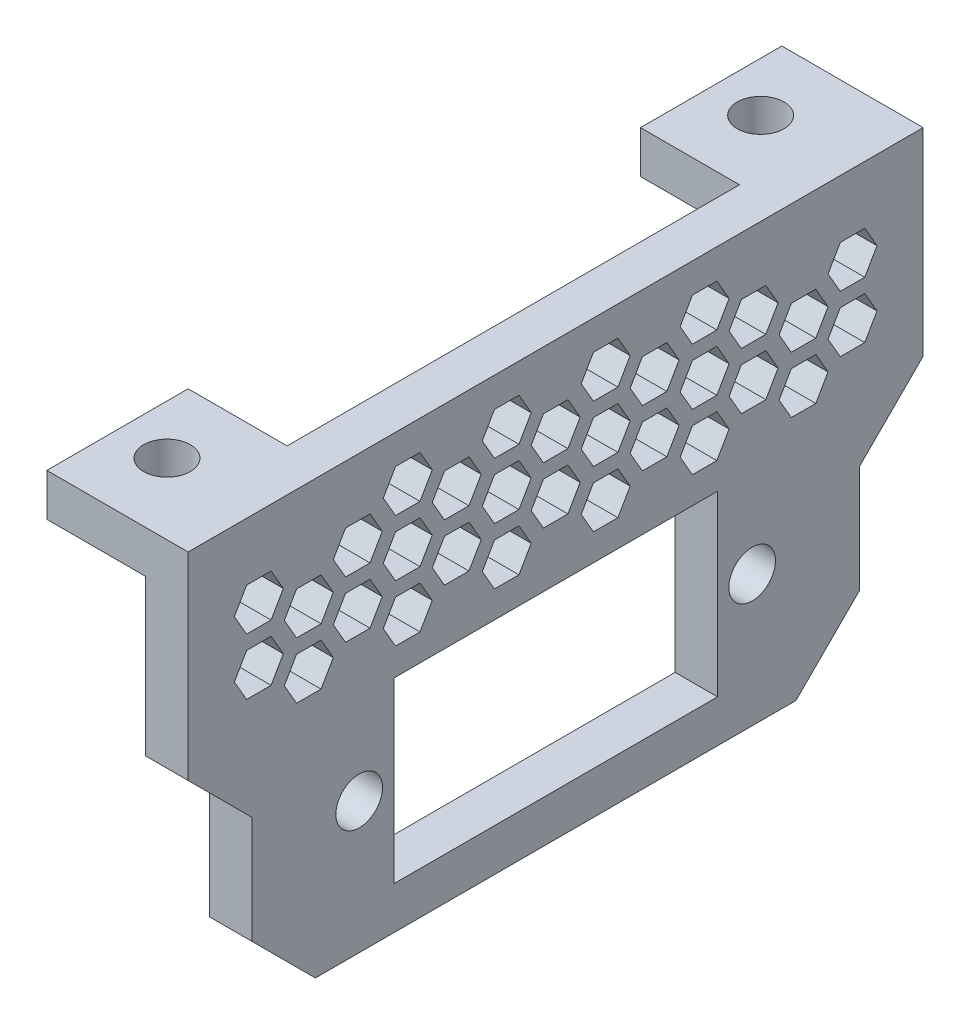
SolidWorks part; units mm, degrees
ref_plane "Front Plane" through (0, 0, 0) normal (0, 0, 1) x (1, 0, 0)
ref_plane "Top Plane" through (0, 0, 0) normal (0, 1, 0) x (1, 0, 0)
ref_plane "Right Plane" through (0, 0, 0) normal (1, 0, 0) x (0, 0, -1)
sketch "Sketch1" plane through (0, 0, 0) normal (1, 0, 0) x (0, 0, -1)
  line L0 (-11.45, 0) -> (11.45, 0)
  line L1 (11.45, 0) -> (11.45, 12.6)
  line L2 (11.45, 12.6) -> (-11.45, 12.6)
  line L3 (-11.45, 12.6) -> (-11.45, 0)
  line L4 (17, -3) -> (-17, -3)
  line L5 (-17, -3) -> (-17, 15.6)
  line L6 (-17, 15.6) -> (17, 15.6)
  line L7 (17, 15.6) -> (17, -3)
  line L8 (0, 0) -> (0, 6.3) construction
  line L9 (-13.9, 6.3) -> (13.9, 6.3)
  circle A0 centre (-13.9, 6.3) radius 1.65
  circle A1 centre (13.9, 6.3) radius 1.65
  point P4 (0, 0)
  point P9 (0, -3)
  point P20 (0, 6.3)
  dimension "D7" = 3.3
  dimension "D8" = 27.8
  dimension "D1" = 22.9
  dimension "D2" = 12.6
  dimension "D3" = 3
  dimension "D4" = 3
  dimension "D5" = 34
  dimension "D6" = 6.3
extrude "Boss-Extrude1" add sketch "Sketch1" along normal blind 3 contours L7 L6 L5 L4 A1 L1 L0 L3 A0 L2 region at (0, -2.6124, 0)
sketch "Sketch2" plane through (0, 0, 0) normal (-1, 0, 0) x (0, 0, 1)
  line L6 (-21.5, 1.5) -> (-17, -3)
  line L8 (17, -3) -> (21.5, 1.5)
  line L9 (21.5, 1.5) -> (21.5, 9.1)
  line L12 (-21.5, 1.5) -> (-21.5, 9.1)
  line L13 (-21.5, 9.1) -> (-26, 13.6)
  line L14 (-26, 13.6) -> (-26, 27.6)
  line L15 (-26, 27.6) -> (26, 27.6)
  line L16 (26, 27.6) -> (26, 13.6)
  line L17 (26, 13.6) -> (21.5, 9.1)
  line L20 (17, -3) -> (17, 15.6)
  line L21 (17, 15.6) -> (-17, 15.6)
  line L22 (-17, 15.6) -> (-17, -3)
  line M10 (-17, 15.6) -> (-17, -3)
  line M12 (17, -3) -> (17, 15.6)
  dimension "D1" = 52
  dimension "D2" = 12
  dimension "D3" = 45
  dimension "D4" = 4.5
  dimension "D5" = 4.5
  dimension "D6" = 135
  dimension "D7" = 14
  dimension "D8" = 14
  dimension "D9" = 9
extrude "Boss-Extrude2" add sketch "Sketch2" against normal blind 3 contours M12 | L13 M10 region at (0, 18.6202, 0)
sketch "Sketch3" plane through (0, 27.6, 0) normal (0, 1, 0) x (1, 0, 0)
  line L1 (0, -26) -> (-7, -26)
  line L2 (0, -26) -> (0, -16)
  line L3 (0, -16) -> (-7, -16)
  line L4 (-7, -26) -> (-7, -16)
  line L5 (3, -26) -> (0, -26) construction
  line L6 (0, 16) -> (-7, 16)
  line L7 (0, 16) -> (0, 26)
  line L8 (0, 26) -> (-7, 26)
  line L9 (-7, 16) -> (-7, 26)
  line L10 (3, 26) -> (0, 26) construction
  circle A0 centre (-3.5, -21) radius 1.65
  circle A1 centre (-3.5, 21) radius 1.65
  dimension "D6" = 3.3
  dimension "D8" = 3.5
  dimension "D9" = 3.5
  dimension "D10" = 5
  dimension "D2" = 42
  dimension "D3" = 10
  dimension "D4" = 10
  dimension "D5" = 7
extrude "Boss-Extrude3" add sketch "Sketch3" against normal blind 3
sketch "Sketch4" plane through (0, 0, 0) normal (-1, 0, 0) x (0, 0, 1)
  line L0 (-15.8038, 20) -> (-16.6699, 21.5)
  line L1 (-19.2679, 18) -> (-20.134, 19.5)
  line L2 (-20.134, 19.5) -> (-21.866, 19.5)
  line L3 (-21.866, 19.5) -> (-22.7321, 18)
  line L4 (-22.7321, 18) -> (-21.866, 16.5)
  line L5 (-21.866, 16.5) -> (-20.134, 16.5)
  line L6 (-20.134, 16.5) -> (-19.2679, 18)
  line L7 (-16.6699, 21.5) -> (-18.4019, 21.5)
  line L8 (-18.4019, 21.5) -> (-19.2679, 20)
  line L9 (-19.2679, 20) -> (-18.4019, 18.5)
  line L10 (-18.4019, 18.5) -> (-16.6699, 18.5)
  line L11 (-16.6699, 18.5) -> (-15.8038, 20)
  line L18 (-19.2679, 22) -> (-20.134, 23.5)
  line L19 (-20.134, 23.5) -> (-21.866, 23.5)
  line L20 (-21.866, 23.5) -> (-22.7321, 22)
  line L21 (-22.7321, 22) -> (-21.866, 20.5)
  line L22 (-21.866, 20.5) -> (-20.134, 20.5)
  line L23 (-20.134, 20.5) -> (-19.2679, 22)
  line L24 (-12.2679, 18) -> (-13.134, 19.5)
  line L25 (-13.134, 19.5) -> (-14.866, 19.5)
  line L26 (-14.866, 19.5) -> (-15.7321, 18)
  line L27 (-15.7321, 18) -> (-14.866, 16.5)
  line L28 (-14.866, 16.5) -> (-13.134, 16.5)
  line L29 (-13.134, 16.5) -> (-12.2679, 18)
  line L30 (-12.2679, 22) -> (-13.134, 23.5)
  line L31 (-13.134, 23.5) -> (-14.866, 23.5)
  line L32 (-14.866, 23.5) -> (-15.7321, 22)
  line L33 (-15.7321, 22) -> (-14.866, 20.5)
  line L34 (-14.866, 20.5) -> (-13.134, 20.5)
  line L35 (-13.134, 20.5) -> (-12.2679, 22)
  line L36 (-5.2679, 18) -> (-6.134, 19.5)
  line L37 (-6.134, 19.5) -> (-7.866, 19.5)
  line L38 (-7.866, 19.5) -> (-8.7321, 18)
  line L39 (-8.7321, 18) -> (-7.866, 16.5)
  line L40 (-7.866, 16.5) -> (-6.134, 16.5)
  line L41 (-6.134, 16.5) -> (-5.2679, 18)
  line L42 (-5.2679, 22) -> (-6.134, 23.5)
  line L43 (-6.134, 23.5) -> (-7.866, 23.5)
  line L44 (-7.866, 23.5) -> (-8.7321, 22)
  line L45 (-8.7321, 22) -> (-7.866, 20.5)
  line L46 (-7.866, 20.5) -> (-6.134, 20.5)
  line L47 (-6.134, 20.5) -> (-5.2679, 22)
  line L48 (1.7321, 18) -> (0.866, 19.5)
  line L49 (0.866, 19.5) -> (-0.866, 19.5)
  line L50 (-0.866, 19.5) -> (-1.7321, 18)
  line L51 (-1.7321, 18) -> (-0.866, 16.5)
  line L52 (-0.866, 16.5) -> (0.866, 16.5)
  line L53 (0.866, 16.5) -> (1.7321, 18)
  line L54 (1.7321, 22) -> (0.866, 23.5)
  line L55 (0.866, 23.5) -> (-0.866, 23.5)
  line L56 (-0.866, 23.5) -> (-1.7321, 22)
  line L57 (-1.7321, 22) -> (-0.866, 20.5)
  line L58 (-0.866, 20.5) -> (0.866, 20.5)
  line L59 (0.866, 20.5) -> (1.7321, 22)
  line L60 (8.7321, 18) -> (7.866, 19.5)
  line L61 (7.866, 19.5) -> (6.134, 19.5)
  line L62 (6.134, 19.5) -> (5.2679, 18)
  line L63 (5.2679, 18) -> (6.134, 16.5)
  line L64 (6.134, 16.5) -> (7.866, 16.5)
  line L65 (7.866, 16.5) -> (8.7321, 18)
  line L66 (8.7321, 22) -> (7.866, 23.5)
  line L67 (7.866, 23.5) -> (6.134, 23.5)
  line L68 (6.134, 23.5) -> (5.2679, 22)
  line L69 (5.2679, 22) -> (6.134, 20.5)
  line L70 (6.134, 20.5) -> (7.866, 20.5)
  line L71 (7.866, 20.5) -> (8.7321, 22)
  line L72 (15.7321, 18) -> (14.866, 19.5)
  line L73 (14.866, 19.5) -> (13.134, 19.5)
  line L74 (13.134, 19.5) -> (12.2679, 18)
  line L75 (12.2679, 18) -> (13.134, 16.5)
  line L76 (13.134, 16.5) -> (14.866, 16.5)
  line L77 (14.866, 16.5) -> (15.7321, 18)
  line L78 (15.7321, 22) -> (14.866, 23.5)
  line L79 (14.866, 23.5) -> (13.134, 23.5)
  line L80 (13.134, 23.5) -> (12.2679, 22)
  line L81 (12.2679, 22) -> (13.134, 20.5)
  line L82 (13.134, 20.5) -> (14.866, 20.5)
  line L83 (14.866, 20.5) -> (15.7321, 22)
  line L84 (22.7321, 18) -> (21.866, 19.5)
  line L85 (21.866, 19.5) -> (20.134, 19.5)
  line L86 (20.134, 19.5) -> (19.2679, 18)
  line L87 (19.2679, 18) -> (20.134, 16.5)
  line L88 (20.134, 16.5) -> (21.866, 16.5)
  line L89 (21.866, 16.5) -> (22.7321, 18)
  line L90 (22.7321, 22) -> (21.866, 23.5)
  line L91 (21.866, 23.5) -> (20.134, 23.5)
  line L92 (20.134, 23.5) -> (19.2679, 22)
  line L93 (19.2679, 22) -> (20.134, 20.5)
  line L94 (20.134, 20.5) -> (21.866, 20.5)
  line L95 (21.866, 20.5) -> (22.7321, 22)
  line L96 (-8.8038, 20) -> (-9.6699, 21.5)
  line L97 (-9.6699, 21.5) -> (-11.4019, 21.5)
  line L98 (-11.4019, 21.5) -> (-12.2679, 20)
  line L99 (-12.2679, 20) -> (-11.4019, 18.5)
  line L100 (-11.4019, 18.5) -> (-9.6699, 18.5)
  line L101 (-9.6699, 18.5) -> (-8.8038, 20)
  line L102 (-8.8038, 24) -> (-9.6699, 25.5)
  line L103 (-9.6699, 25.5) -> (-11.4019, 25.5)
  line L104 (-11.4019, 25.5) -> (-12.2679, 24)
  line L105 (-12.2679, 24) -> (-11.4019, 22.5)
  line L106 (-11.4019, 22.5) -> (-9.6699, 22.5)
  line L107 (-9.6699, 22.5) -> (-8.8038, 24)
  line L108 (-1.8038, 20) -> (-2.6699, 21.5)
  line L109 (-2.6699, 21.5) -> (-4.4019, 21.5)
  line L110 (-4.4019, 21.5) -> (-5.2679, 20)
  line L111 (-5.2679, 20) -> (-4.4019, 18.5)
  line L112 (-4.4019, 18.5) -> (-2.6699, 18.5)
  line L113 (-2.6699, 18.5) -> (-1.8038, 20)
  line L114 (-1.8038, 24) -> (-2.6699, 25.5)
  line L115 (-2.6699, 25.5) -> (-4.4019, 25.5)
  line L116 (-4.4019, 25.5) -> (-5.2679, 24)
  line L117 (-5.2679, 24) -> (-4.4019, 22.5)
  line L118 (-4.4019, 22.5) -> (-2.6699, 22.5)
  line L119 (-2.6699, 22.5) -> (-1.8038, 24)
  line L120 (5.1962, 20) -> (4.3301, 21.5)
  line L121 (4.3301, 21.5) -> (2.5981, 21.5)
  line L122 (2.5981, 21.5) -> (1.7321, 20)
  line L123 (1.7321, 20) -> (2.5981, 18.5)
  line L124 (2.5981, 18.5) -> (4.3301, 18.5)
  line L125 (4.3301, 18.5) -> (5.1962, 20)
  line L126 (5.1962, 24) -> (4.3301, 25.5)
  line L127 (4.3301, 25.5) -> (2.5981, 25.5)
  line L128 (2.5981, 25.5) -> (1.7321, 24)
  line L129 (1.7321, 24) -> (2.5981, 22.5)
  line L130 (2.5981, 22.5) -> (4.3301, 22.5)
  line L131 (4.3301, 22.5) -> (5.1962, 24)
  line L132 (12.1962, 20) -> (11.3301, 21.5)
  line L133 (11.3301, 21.5) -> (9.5981, 21.5)
  line L134 (9.5981, 21.5) -> (8.7321, 20)
  line L135 (8.7321, 20) -> (9.5981, 18.5)
  line L136 (9.5981, 18.5) -> (11.3301, 18.5)
  line L137 (11.3301, 18.5) -> (12.1962, 20)
  line L138 (12.1962, 24) -> (11.3301, 25.5)
  line L139 (11.3301, 25.5) -> (9.5981, 25.5)
  line L140 (9.5981, 25.5) -> (8.7321, 24)
  line L141 (8.7321, 24) -> (9.5981, 22.5)
  line L142 (9.5981, 22.5) -> (11.3301, 22.5)
  line L143 (11.3301, 22.5) -> (12.1962, 24)
  line L144 (19.1962, 20) -> (18.3301, 21.5)
  line L145 (18.3301, 21.5) -> (16.5981, 21.5)
  line L146 (16.5981, 21.5) -> (15.7321, 20)
  line L147 (15.7321, 20) -> (16.5981, 18.5)
  line L148 (16.5981, 18.5) -> (18.3301, 18.5)
  line L149 (18.3301, 18.5) -> (19.1962, 20)
  line L156 (-8.8038, 16) -> (-9.6699, 17.5)
  line L157 (-9.6699, 17.5) -> (-11.4019, 17.5)
  line L158 (-11.4019, 17.5) -> (-12.2679, 16)
  line L159 (-12.2679, 16) -> (-11.4019, 14.5)
  line L160 (-11.4019, 14.5) -> (-9.6699, 14.5)
  line L161 (-9.6699, 14.5) -> (-8.8038, 16)
  line L162 (-8.8038, 20) -> (-9.6699, 21.5)
  line L163 (-9.6699, 21.5) -> (-11.4019, 21.5)
  line L164 (-11.4019, 21.5) -> (-12.2679, 20)
  line L165 (-12.2679, 20) -> (-11.4019, 18.5)
  line L166 (-11.4019, 18.5) -> (-9.6699, 18.5)
  line L167 (-9.6699, 18.5) -> (-8.8038, 20)
  line L168 (-1.8038, 16) -> (-2.6699, 17.5)
  line L169 (-2.6699, 17.5) -> (-4.4019, 17.5)
  line L170 (-4.4019, 17.5) -> (-5.2679, 16)
  line L171 (-5.2679, 16) -> (-4.4019, 14.5)
  line L172 (-4.4019, 14.5) -> (-2.6699, 14.5)
  line L173 (-2.6699, 14.5) -> (-1.8038, 16)
  line L174 (-1.8038, 20) -> (-2.6699, 21.5)
  line L175 (-2.6699, 21.5) -> (-4.4019, 21.5)
  line L176 (-4.4019, 21.5) -> (-5.2679, 20)
  line L177 (-5.2679, 20) -> (-4.4019, 18.5)
  line L178 (-4.4019, 18.5) -> (-2.6699, 18.5)
  line L179 (-2.6699, 18.5) -> (-1.8038, 20)
  line L180 (5.1962, 16) -> (4.3301, 17.5)
  line L181 (4.3301, 17.5) -> (2.5981, 17.5)
  line L182 (2.5981, 17.5) -> (1.7321, 16)
  line L183 (1.7321, 16) -> (2.5981, 14.5)
  line L184 (2.5981, 14.5) -> (4.3301, 14.5)
  line L185 (4.3301, 14.5) -> (5.1962, 16)
  line L186 (5.1962, 20) -> (4.3301, 21.5)
  line L187 (4.3301, 21.5) -> (2.5981, 21.5)
  line L188 (2.5981, 21.5) -> (1.7321, 20)
  line L189 (1.7321, 20) -> (2.5981, 18.5)
  line L190 (2.5981, 18.5) -> (4.3301, 18.5)
  line L191 (4.3301, 18.5) -> (5.1962, 20)
  line L192 (12.1962, 16) -> (11.3301, 17.5)
  line L193 (11.3301, 17.5) -> (9.5981, 17.5)
  line L194 (9.5981, 17.5) -> (8.7321, 16)
  line L195 (8.7321, 16) -> (9.5981, 14.5)
  line L196 (9.5981, 14.5) -> (11.3301, 14.5)
  line L197 (11.3301, 14.5) -> (12.1962, 16)
  line L198 (12.1962, 20) -> (11.3301, 21.5)
  line L199 (11.3301, 21.5) -> (9.5981, 21.5)
  line L200 (9.5981, 21.5) -> (8.7321, 20)
  line L201 (8.7321, 20) -> (9.5981, 18.5)
  line L202 (9.5981, 18.5) -> (11.3301, 18.5)
  line L203 (11.3301, 18.5) -> (12.1962, 20)
  line L204 (19.1962, 16) -> (18.3301, 17.5)
  line L205 (18.3301, 17.5) -> (16.5981, 17.5)
  line L206 (16.5981, 17.5) -> (15.7321, 16)
  line L207 (15.7321, 16) -> (16.5981, 14.5)
  line L208 (16.5981, 14.5) -> (18.3301, 14.5)
  line L209 (18.3301, 14.5) -> (19.1962, 16)
  line L210 (19.1962, 20) -> (18.3301, 21.5)
  line L211 (18.3301, 21.5) -> (16.5981, 21.5)
  line L212 (16.5981, 21.5) -> (15.7321, 20)
  line L213 (15.7321, 20) -> (16.5981, 18.5)
  line L214 (16.5981, 18.5) -> (18.3301, 18.5)
  line L215 (18.3301, 18.5) -> (19.1962, 20)
  line L216 (-15.8038, 16) -> (-16.6699, 17.5)
  line L217 (-16.6699, 17.5) -> (-18.4019, 17.5)
  line L218 (-18.4019, 17.5) -> (-19.2679, 16)
  line L219 (-19.2679, 16) -> (-18.4019, 14.5)
  line L220 (-18.4019, 14.5) -> (-16.6699, 14.5)
  line L221 (-16.6699, 14.5) -> (-15.8038, 16)
  line L222 (-15.8038, 20) -> (-16.6699, 21.5)
  line L223 (-16.6699, 21.5) -> (-18.4019, 21.5)
  line L224 (-18.4019, 21.5) -> (-19.2679, 20)
  line L225 (-19.2679, 20) -> (-18.4019, 18.5)
  line L226 (-18.4019, 18.5) -> (-16.6699, 18.5)
  line L227 (-16.6699, 18.5) -> (-15.8038, 20)
  line L228 (-16.6699, 25.5) -> (-18.4019, 25.5) [skipped]
  line L229 (-18.4019, 22.5) -> (-16.6699, 22.5) [skipped]
  line L230 (-19.2679, 24) -> (-18.4019, 22.5) [skipped]
  line L231 (-18.4019, 25.5) -> (-19.2679, 24) [skipped]
  line L232 (-15.8038, 24) -> (-16.6699, 25.5) [skipped]
  line L233 (-16.6699, 22.5) -> (-15.8038, 24) [skipped]
  circle A0 centre (-21, 18) radius 1.5 construction
  dimension "D3" = 3
  dimension "D1" = 21
  dimension "D2" = 18
  dimension "D4" = 2
  dimension "D5" = 2
  dimension "D6" = 7
  dimension "D7" = 6
  dimension "D8" = 2
extrude "Cut-Extrude1" cut sketch "Sketch4" against normal blind 10 contours L124 L125 L120 L121 L122 L123 | L58 L59 L54 L55 L56 L57 | L52 L53 L48 L49 L50 L51 | L112 L113 L108 L109 L110 L111 | L118 L119 L114 L115 L116 L117 | L172 L173 L168 L169 L170 L171 | L40 L41 L36 L37 L38 L39 | L46 L47 L42 L43 L44 L45 | L106 L107 L102 L103 L104 L105 | L100 L101 L96 L97 L98 L99 | L160 L161 L156 L157 L158 L159 | L28 L29 L24 L25 L26 L27 | L34 L35 L30 L31 L32 L33 | L10 L11 L0 L7 L8 L9 | L220 L221 L216 L217 L218 L219 | L5 L6 L1 L2 L3 L4 | L22 L23 L18 L19 L20 L21 | L184 L185 L180 L181 L182 L183 | L130 L131 L126 L127 L128 L129 | L70 L71 L66 L67 L68 L69 | L136 L137 L132 L133 L134 L135 | L142 L143 L138 L139 L140 L141 | L196 L197 L192 L193 L194 L195 | L76 L77 L72 L73 L74 L75 | L82 L83 L78 L79 L80 L81 | L148 L149 L144 L145 L146 L147 | L208 L209 L204 L205 L206 L207 | L88 L89 L84 L85 L86 L87 | L94 L95 L90 L91 L92 L93 | L64 L65 L60 L61 L62 L63 region at (0, 20, -17.5359) region at (0, 18, -21) region at (0, 22, -21) region at (0, 18, -14) region at (0, 22, -14) region at (0, 18, -7) region at (0, 22, -7) region at (0, 18, 0) region at (0, 22, 0) region at (0, 18, 7) region at (0, 22, 7) region at (0, 18, 14) region at (0, 22, 14) region at (0, 18, 21) region at (0, 22, 21) region at (0, 20, -10.5359) region at (0, 24, -10.5359) region at (0, 20, -3.5359) region at (0, 24, -3.5359) region at (0, 20, 3.4641) region at (0, 24, 3.4641) region at (0, 20, 10.4641) region at (0, 24, 10.4641) region at (0, 20, 17.4641) region at (0, 16, -10.5359) region at (0, 16, -3.5359) region at (0, 16, 3.4641) region at (0, 16, 10.4641) region at (0, 16, 17.4641) region at (0, 16, -17.5359)
